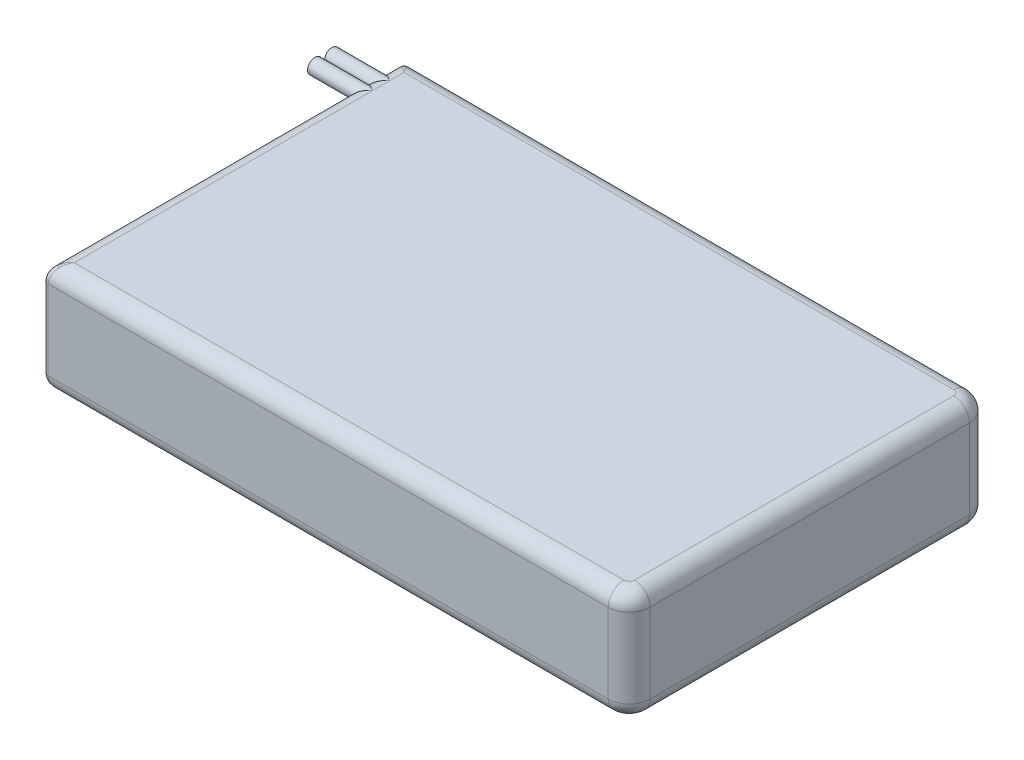
SolidWorks part; units mm, degrees
ref_plane "Front Plane" through (0, 0, 0) normal (0, 0, 1) x (1, 0, 0)
ref_plane "Top Plane" through (0, 0, 0) normal (0, 1, 0) x (1, 0, 0)
ref_plane "Right Plane" through (0, 0, 0) normal (1, 0, 0) x (0, 0, -1)
sketch "Sketch1" plane through (0, 0, 0) normal (0, 1, 0) x (1, 0, 0)
  line L1 (-27.5, -17.25) -> (26, -17.25)
  line L2 (-28, -16.75) -> (-28, 16.75)
  line L3 (-27.5, 17.25) -> (26, 17.25)
  line L4 (28, -15.25) -> (28, 15.25)
  line L5 (-28, -17.25) -> (28, 17.25) construction
  line L6 (-28, 17.25) -> (28, -17.25) construction
  arc A0 (26, 17.25) -> (28, 15.25) centre (26, 15.25) cw
  arc A1 (26, -17.25) -> (28, -15.25) centre (26, -15.25) ccw
  arc A2 (-27.5, -17.25) -> (-28, -16.75) centre (-27.5, -16.75) cw
  arc A3 (-28, 16.75) -> (-27.5, 17.25) centre (-27.5, 16.75) cw
  point P0 (0, 0)
  dimension "D3" = 2
  dimension "D4" = 0.5
  dimension "D1" = 56
  dimension "D2" = 34.5
extrude "Boss-Extrude1" add sketch "Sketch1" along normal blind 10.6
fillet "Fillet1" radius 1.5 16 edges at (-0.75, 0, -17.25) (-27.8536, 0, -17.1036) (-28, 0, 0) (-27.8536, 0, 17.1036) (-0.75, 0, 17.25) (27.4142, 0, 16.6642) (28, 0, 0) (27.4142, 0, -16.6642) (28, 10.6, 0) (27.4142, 10.6, 16.6642) (-0.75, 10.6, 17.25) (-27.8536, 10.6, 17.1036) (-28, 10.6, 0) (-27.8536, 10.6, -17.1036) (-0.75, 10.6, -17.25) (27.4142, 10.6, -16.6642)
sketch "Sketch2" plane through (-28, 0, 0) normal (-1, 0, 0) x (0, 0, 1)
  circle A0 centre (-14.3576, 9.8973) radius 0.7027
  circle A1 centre (-12.7309, 9.8973) radius 0.7027
extrude "Boss-Extrude2" add sketch "Sketch2" along normal blind 4 and the other way blind 4
